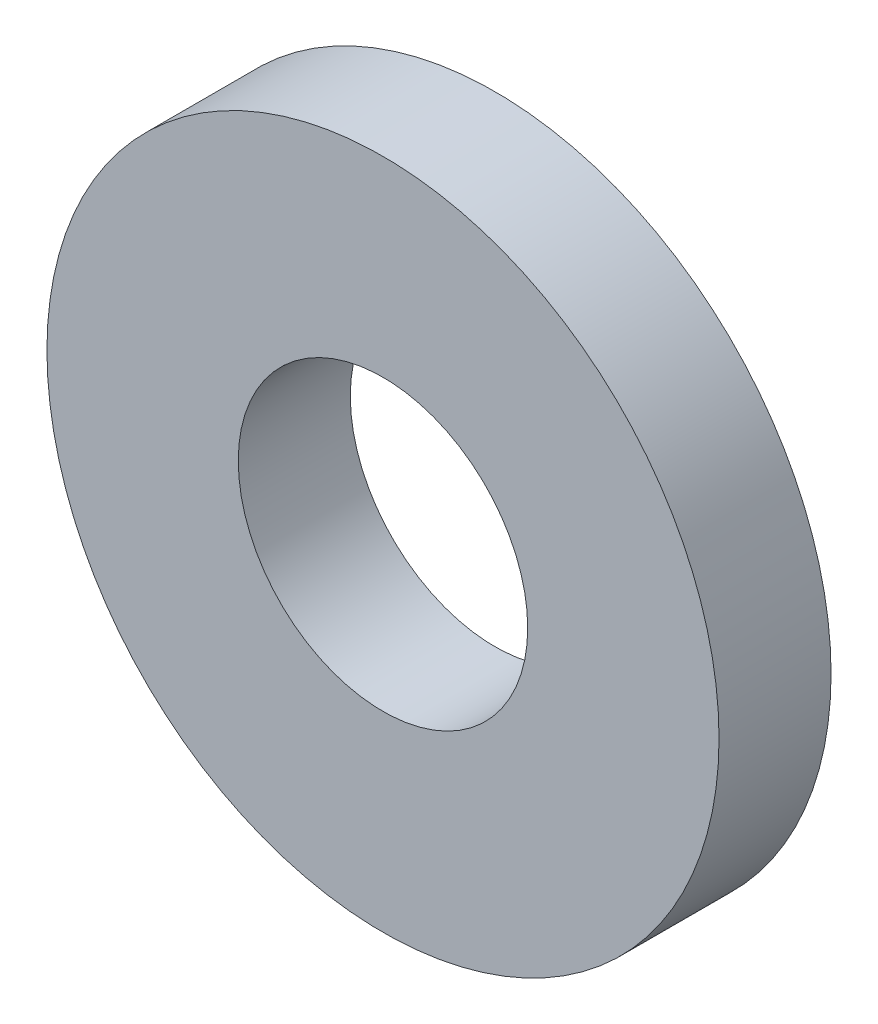
SolidWorks part; units mm, degrees
material "ABS"
ref_plane "Front Plane" through (0, 0, 0) normal (0, 0, 1) x (1, 0, 0)
ref_plane "Top Plane" through (0, 0, 0) normal (0, 1, 0) x (1, 0, 0)
ref_plane "Right Plane" through (0, 0, 0) normal (1, 0, 0) x (0, 0, -1)
sketch "Sketch1" plane through (0, 0, 0) normal (0, 0, 1) x (1, 0, 0)
  circle A0 centre (0, 0) radius 9.525
  dimension "D1" = 19.05
extrude "Boss-Extrude1" add sketch "Sketch1" along normal mid plane 3.175
hole_wizard "5/16 Clearance Hole1" positions "Sketch2" profile "Sketch3" hole size "5/16" standard "ANSI Inch" end condition through all
sketch "Sketch2" plane through (0, 0, 1.5875) normal (0, 0, 1) x (1, 0, 0)
  point P0 (0, 0)
sketch "Sketch3" plane through (0, 0, 1.5875) normal (1, 0, 0) x (0, -1, 0)
  line L0 (0, 0) -> (0, 3.175)
  line L1 (0, 3.175) -> (4.1021, 3.175)
  line L2 (4.1021, 3.175) -> (4.1021, 0)
  line L5 (4.1021, 0) -> (0, 0)
  line L11 (0, -6.35) -> (0, 107.95) construction
  dimension "Thru Hole Dia." = 8.2042
  dimension "Thru Hole Depth" = 3.175
equation "\"D1@Boss-Extrude1\"=0.125in"
equation "\"D1@Sketch1\"=0.75in"
